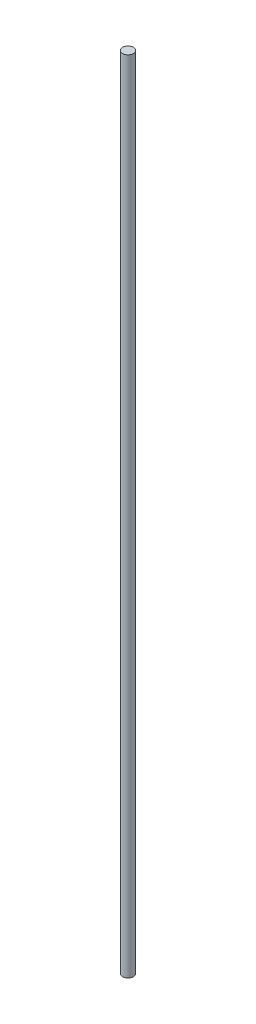
SolidWorks part; units mm, degrees
ref_plane "Front Plane" through (0, 0, 0) normal (0, 0, 1) x (1, 0, 0)
ref_plane "Top Plane" through (0, 0, 0) normal (0, 1, 0) x (1, 0, 0)
ref_plane "Right Plane" through (0, 0, 0) normal (1, 0, 0) x (0, 0, -1)
sketch "Sketch1" plane through (0, 0, 0) normal (0, 1, 0) x (1, 0, 0)
  circle A0 centre (0, 0) radius 6.35
  dimension "D1" = 12.7
extrude "Boss-Extrude1" add sketch "Sketch1" along normal blind 934.4
